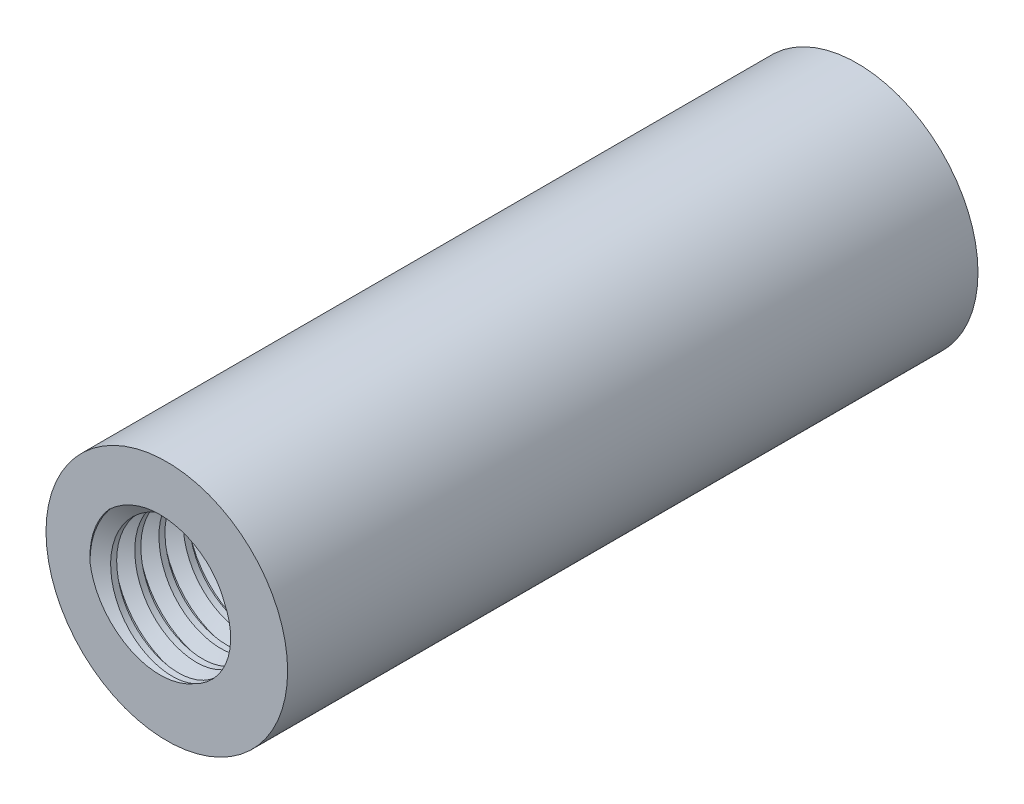
SolidWorks part; units mm, degrees
material "사용자정의 플라스틱"
ref_plane "정면" through (0, 0, 0) normal (0, 0, 1) x (1, 0, 0)
ref_plane "윗면" through (0, 0, 0) normal (0, 1, 0) x (1, 0, 0)
ref_plane "우측면" through (0, 0, 0) normal (1, 0, 0) x (0, 0, -1)
sketch "스케치1" plane through (0, 0, 0) normal (0, 0, 1) x (1, 0, 0)
  circle A0 centre (0, 0) radius 3.5
  dimension "D1" = 7
extrude "보스-돌출1" add sketch "스케치1" along normal blind 20
hole_wizard "M4x0.7 Helicoil용 탭 구멍1" positions "스케치2" profile "스케치4" tap size "M4x0.7" standard "Helicoil® Metric" end condition through all
sketch "스케치2" plane through (0, 0, 20) normal (0, 0, 1) x (1, 0, 0)
  point P0 (0, 0)
sketch "스케치4" plane through (0, 0, 20) normal (1, 0, 0) x (0, -1, 0)
  line L0 (0, 0) -> (0, 20)
  line L1 (0, 20) -> (1.85, 20)
  line L2 (1.85, 20) -> (1.85, 0)
  line L5 (1.85, 0) -> (0, 0)
  line L11 (0, -6.35) -> (0, 107.95) construction
  dimension "관통 탭 드릴 지름" = 3.7
  dimension "관통 탭 드릴 깊이" = 20
thread "나사산1" pitch 0.7 method cut profile "나사산 프로파일1" start angle 0, offset 1, length 25, pitch 0.7, diameter 3.7
ref_plane "평면1" through (-1.85, 0, 21) normal (0, -1, 0) x (-1, 0, 0)
sketch "나사산 프로파일1" plane through (-1.85, 0, 21) normal (0, -1, 0) x (-1, 0, 0)
  line L0 (0, 0) -> (0, 0.7) construction
  line L1 (0, 0) -> (0.3789, 0.2187)
  line L2 (0.3789, 0.2187) -> (0.3789, 0.3062)
  line L3 (0.3789, 0.3062) -> (0, 0.525)
  line L4 (0.3789, 0.2625) -> (0, 0.2625) construction
  line L11 (0, 0) -> (0, 0.525)
  point P2 (0, 0)
  dimension "Pitch" = 0.7
  dimension "Profile_Angle" = 60
  dimension "Profile_Land" = 0.0875
  dimension "Profile_Height" = 0.3789
